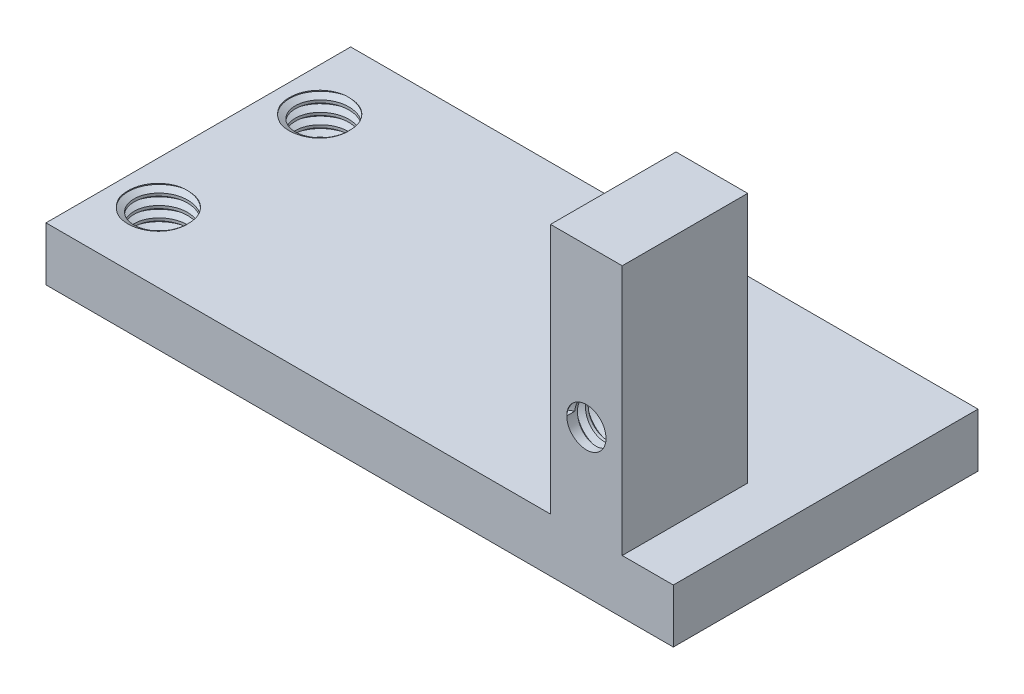
SolidWorks part; units mm, degrees
ref_plane "Front Plane" through (0, 0, 0) normal (0, 0, 1) x (1, 0, 0)
ref_plane "Top Plane" through (0, 0, 0) normal (0, 1, 0) x (1, 0, 0)
ref_plane "Right Plane" through (0, 0, 0) normal (1, 0, 0) x (0, 0, -1)
sketch "Sketch1" plane through (0, 0, 0) normal (0, 1, 0) x (1, 0, 0)
  line L1 (-102.4004, -124.6852) -> (-72.4004, -124.6852)
  line L3 (-95.4004, -141.6852) -> (-72.4004, -141.6852)
  line L4 (-72.4004, -124.6852) -> (-72.4004, -141.6852)
  line L5 (-102.4004, -124.6852) -> (-107.4004, -124.6852)
  line L7 (-95.4004, -141.6852) -> (-107.4004, -141.6852)
  line L8 (-107.4004, -124.6852) -> (-107.4004, -141.6852)
  dimension "D1" = 30
  dimension "D2" = 17
  dimension "D3" = 5
extrude "Boss-Extrude1" add sketch "Sketch1" along normal blind 3
sketch "Sketch3" plane through (0, 0, 0) normal (0, -1, 0) x (1, 0, 0)
  line L0 (-107.4004, 124.6852) -> (-107.4004, 141.6852) construction
  circle A1 centre (-104.9004, 128.6852) radius 1.5
  circle A2 centre (-104.9004, 137.6852) radius 1.5
  dimension "D2" = 3
  dimension "D3" = 3
  dimension "D1" = 2.5
  dimension "D4" = 2.5
  dimension "D5" = 9
extrude "Cut-Extrude1" cut sketch "Sketch3" against normal blind 6
sketch "Sketch4" plane through (0, 3, 0) normal (0, 1, 0) x (1, 0, 0)
  line L0 (-107.4004, -141.6852) -> (-72.4004, -141.6852) construction
  line L1 (-75.2503, -141.6852) -> (-79.2503, -141.6852)
  line L2 (-75.2503, -141.6852) -> (-75.2503, -134.6852)
  line L4 (-79.2503, -141.6852) -> (-79.2503, -134.6852)
  line L6 (-79.2503, -134.6852) -> (-75.2503, -134.6852)
  dimension "D1" = 7
extrude "Boss-Extrude2" add sketch "Sketch4" along normal blind 14
sketch "Sketch5" plane through (0, 0, 141.6852) normal (0, 0, 1) x (1, 0, 0)
  circle A0 centre (-77.2504, 8.2) radius 1.0954
extrude "Cut-Extrude2" cut sketch "Sketch5" against normal blind 5
thread "Thread1" pitch 0.6 start angle 0, offset 0, length 10, pitch 0.6, diameter 3
ref_plane "Plane1" through (-103.4004, 0, 137.6852) normal (0, 0, 1) x (1, 0, 0)
sketch "Thread Profile1" plane through (-103.4004, 0, 137.6852) normal (0, 0, 1) x (1, 0, 0)
  line L0 (0, 0) -> (0, 0.6) construction
  line L1 (0, 0) -> (0.3248, 0.1875)
  line L2 (0.3248, 0.1875) -> (0.3248, 0.2625)
  line L3 (0.3248, 0.2625) -> (0, 0.45)
  line L4 (0.3248, 0.225) -> (0, 0.225) construction
  line L11 (0, 0) -> (0, 0.45)
  point P2 (0, 0)
  dimension "Pitch" = 0.6
  dimension "Profile_Angle" = 60
  dimension "Profile_Land" = 0.075
  dimension "Profile_Height" = 0.3248
thread "Thread2" pitch 0.6 profile "Thread Profile2" start angle 0, offset 0, length 10, pitch 0.6, diameter 3
ref_plane "Plane2" through (-103.4004, 0, 128.6852) normal (0, 0, 1) x (1, 0, 0)
sketch "Thread Profile2" plane through (-103.4004, 0, 128.6852) normal (0, 0, 1) x (1, 0, 0)
  line L0 (0, 0) -> (0, 0.6) construction
  line L1 (0, 0) -> (0.3248, 0.1875)
  line L2 (0.3248, 0.1875) -> (0.3248, 0.2625)
  line L3 (0.3248, 0.2625) -> (0, 0.45)
  line L4 (0.3248, 0.225) -> (0, 0.225) construction
  line L11 (0, 0) -> (0, 0.45)
  point P2 (0, 0)
  dimension "Pitch" = 0.6
  dimension "Profile_Angle" = 60
  dimension "Profile_Land" = 0.075
  dimension "Profile_Height" = 0.3248
thread "Thread3" pitch 0.6 profile "Thread Profile3" start angle 0, offset 0, length 5, pitch 0.6, diameter 2.1908
ref_plane "Plane3" through (-78.3458, 8.2, 141.6852) normal (0, -1, 0) x (-1, 0, 0)
sketch "Thread Profile3" plane through (-78.3458, 8.2, 141.6852) normal (0, -1, 0) x (-1, 0, 0)
  line L0 (0, 0) -> (0, 0.6) construction
  line L1 (0, 0) -> (0.3248, 0.1875)
  line L2 (0.3248, 0.1875) -> (0.3248, 0.2625)
  line L3 (0.3248, 0.2625) -> (0, 0.45)
  line L4 (0.3248, 0.225) -> (0, 0.225) construction
  line L11 (0, 0) -> (0, 0.45)
  point P2 (0, 0)
  dimension "Pitch" = 0.6
  dimension "Profile_Angle" = 60
  dimension "Profile_Land" = 0.075
  dimension "Profile_Height" = 0.3248
